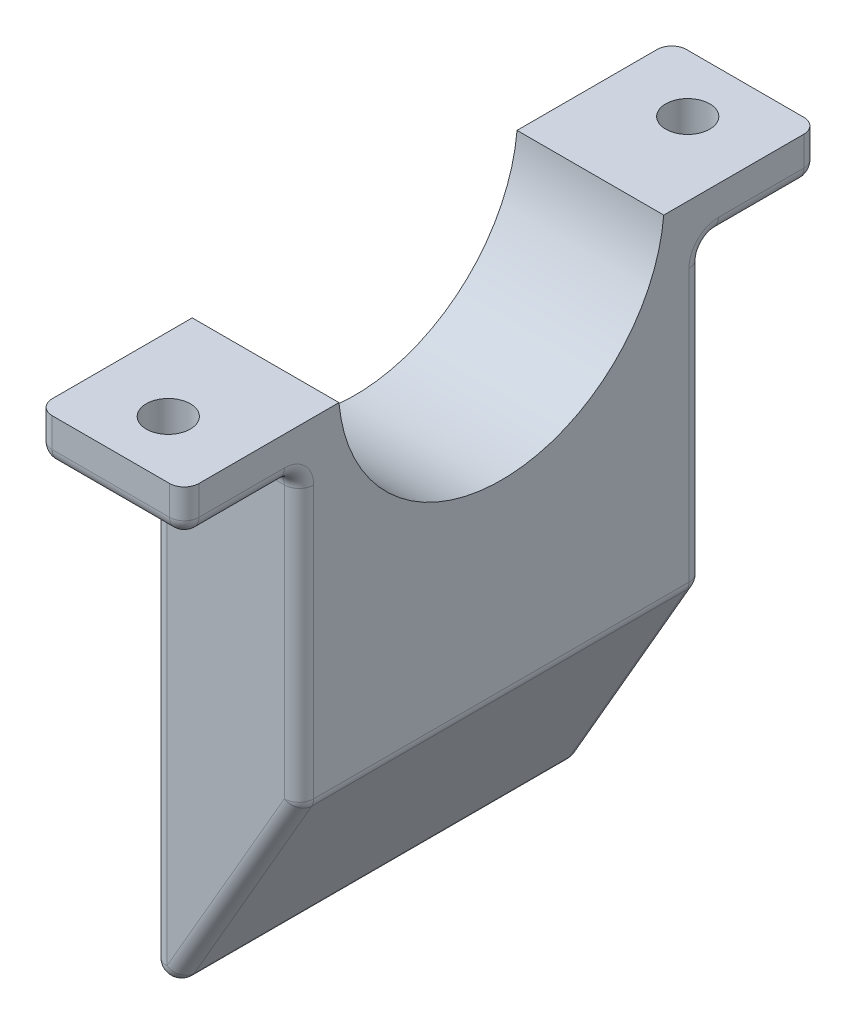
SolidWorks part; units mm, degrees
ref_plane "Front Plane" through (0, 0, 0) normal (0, 0, 1) x (1, 0, 0)
ref_plane "Top Plane" through (0, 0, 0) normal (0, 1, 0) x (1, 0, 0)
ref_plane "Right Plane" through (0, 0, 0) normal (1, 0, 0) x (0, 0, -1)
sketch "Sketch4" plane through (0, 0, 0) normal (1, 0, 0) x (0, 0, -1)
  line L2 (-21.6125, -1) -> (-21.6125, -4)
  line L3 (-21.6125, -4) -> (-13.7899, -4)
  line L4 (21.6125, -1) -> (21.6125, -4)
  line L5 (13.7899, -4) -> (21.6125, -4)
  line L7 (-21.6125, -1) -> (-11.0674, -1)
  line L8 (11.0674, -1) -> (21.6125, -1)
  line L10 (-13.7899, -4) -> (-13.7899, -41.1125)
  line L11 (13.7899, -4) -> (13.7899, -41.1125)
  line L12 (-13.7899, -41.1125) -> (13.7899, -41.1125)
  arc A0 (-11.0674, -1) -> (11.0674, -1) centre (0, 0) ccw
  point P3 (0, -11.1125)
  dimension "D2" = 22.225
  dimension "D3" = 22.1348
  dimension "D4" = 30
  dimension "D1" = 3
extrude "Clamp Extrude" add sketch "Sketch4" along normal blind 10
sketch "Hole" plane through (0, -4, 0) normal (0, -1, 0) x (1, 0, 0)
  line L4 (0, 21.6125) -> (0, 13.7899) construction
  line L5 (10, 21.6125) -> (10, 13.7899) construction
  line L10 (10, 21.6125) -> (0, 21.6125) construction
  line L11 (10, 13.7899) -> (0, 13.7899) construction
  circle A0 centre (5, 17.7012) radius 1.5
  circle A2 centre (5, -17.7012) radius 1.5
  dimension "D1" = 3
  dimension "D4" = 10
  dimension "D5" = 5
  dimension "D2" = 7.8226
  dimension "D3" = 3.9113
extrude "Holes Cut-Extrude" cut sketch "Hole" against normal through all contours A0 region at (5, -4, 17.7012)
extrude "Cut-Extrude2" cut sketch "Hole<3>" against normal through all
sketch "Hole<3>" plane through (0, -4, 0) normal (0, -1, 0) x (1, 0, 0) same geometry as "Hole"
sketch "Sketch10" plane through (0, 0, -13.7899) normal (0, 0, -1) x (-1, 0, 0)
  line L0 (0, -41.1125) -> (-10, -23.792)
  line L1 (-10, -41.1125) -> (-10, -4) construction
  line L2 (-10, -23.792) -> (-10, -41.1125)
  line L3 (-10, -41.1125) -> (0, -41.1125)
  dimension "D1" = 30
extrude "Cut-Extrude3" cut sketch "Sketch10" against normal through all
fillet "Fillet2" radius 1 16 edges at (10, -13.896, 13.7899) (0, -4, 17.7012) (0, -4, -17.7012) (10, -4, 17.7012) (5, -4, 21.6125) (5, -4, 13.7899) (5, -4, -21.6125) (5, -4, -13.7899) (10, -4, -17.7012) (10, -23.792, 0) (5, -32.4522, -13.7899) (5, -32.4522, 13.7899) (0, -41.1125, 0) (0, -22.5562, 13.7899) (0, -22.5562, -13.7899) (10, -13.896, -13.7899)
fillet "Fillet3" radius 1 8 edges at (0.2929, -3.7071, -21.3196) (9.7071, -3.7071, -21.3196) (9.7071, -3.7071, 21.3196) (0.2929, -3.7071, 21.3196) (0, -2, -21.6125) (10, -2, -21.6125) (10, -2, 21.6125) (0, -2, 21.6125)
equation "\"D5@Hole\"=\"D4@Hole\"/2"
equation "\"D3@Hole\"=\"D2@Hole\"/2"
